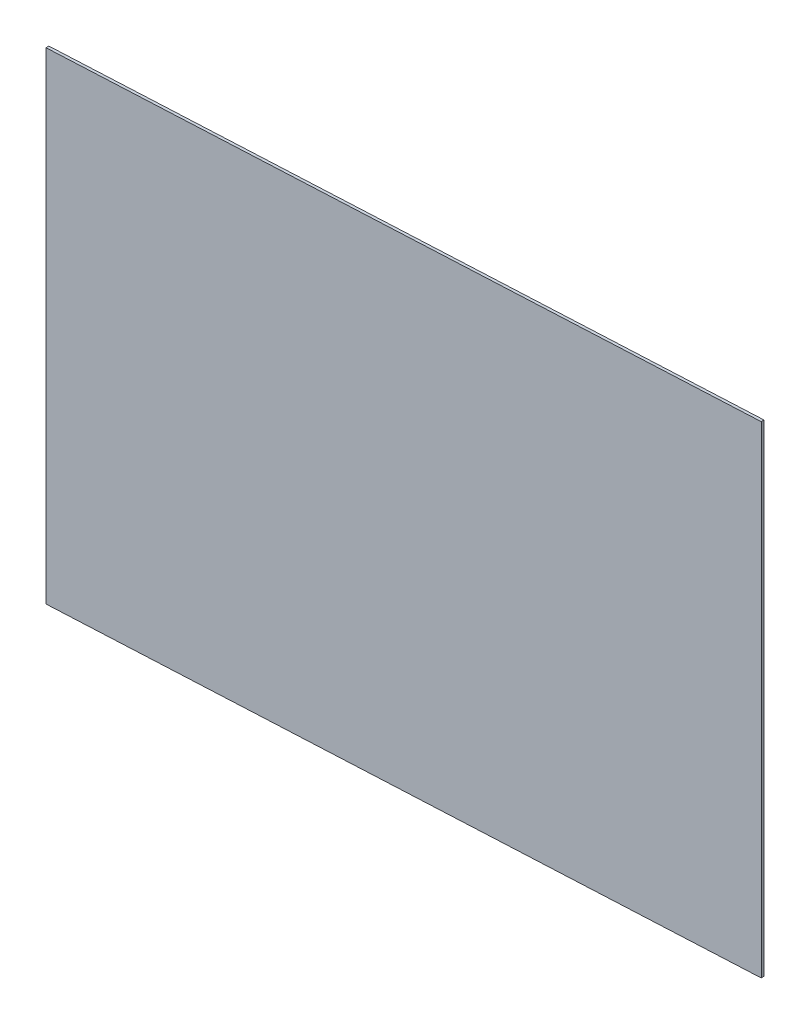
SolidWorks part; units mm, degrees
material "PPS"
ref_plane "Płaszczyzna XY" through (0, 0, 0) normal (0, 0, 1) x (1, 0, 0)
ref_plane "Płaszczyzna XZ" through (0, 0, 0) normal (0, 1, 0) x (1, 0, 0)
ref_plane "Płaszczyzna YZ" through (0, 0, 0) normal (1, 0, 0) x (0, 0, -1)
ref_plane "Płaszczyzna1" through (2.3197, 0, 46.8075) normal (0.0495, 0, 0.9988) x (0.9988, 0, -0.0495)
ref_axis "Oś1" through (-920, -312.6773, 80) along (0, 1, 0)
ref_axis "Oś2" through (-1485, -210, 108) along (0, 1, 0)
ref_axis "Oś3" through (-920.6362, -210, 80.0312) along (-0.9988, 0, 0.049)
ref_axis "Oś4" through (-920.6362, 210, 80.0312) along (-0.9988, 0, 0.049)
sketch "Szkic3" plane through (2.3197, 0, 46.8075) normal (0.0495, 0, 0.9988) x (0.9988, 0, -0.0495)
  line L0 (-922.8321, -312.6773) -> (-922.8321, 312.6773) construction
  line L1 (-796.3321, 0) -> (-1728.4665, 0) construction
  line L3 (-796.3321, 0) -> (-796.3321, -195.25)
  line L4 (-796.3321, 0) -> (-1072.8321, 0) construction
  line L5 (-1349.3321, 195.25) -> (-796.3321, 195.25)
  line L6 (-1349.3321, 195.25) -> (-1349.3321, -195.25)
  line L7 (-796.3321, 195.25) -> (-796.3321, -195.25)
  line L8 (-1349.3321, -195.25) -> (-796.3321, -195.25)
  line L9 (-1349.3321, 195.25) -> (-796.3321, -195.25) construction
  line L10 (-796.3321, 195.25) -> (-1349.3321, -195.25) construction
  dimension "D1" = 553
  dimension "D2" = 150
  dimension "D3" = 390.5
extrude "Dodanie-wyciągnięcie1" add sketch "Szkic3" along normal blind 2.3 contours L7 L5 L6 L8
ref_plane "Płaszczyzna2" through (-792.9225, -195.25, 88.5205) normal (0, -1, 0) x (-1, 0, 0)
